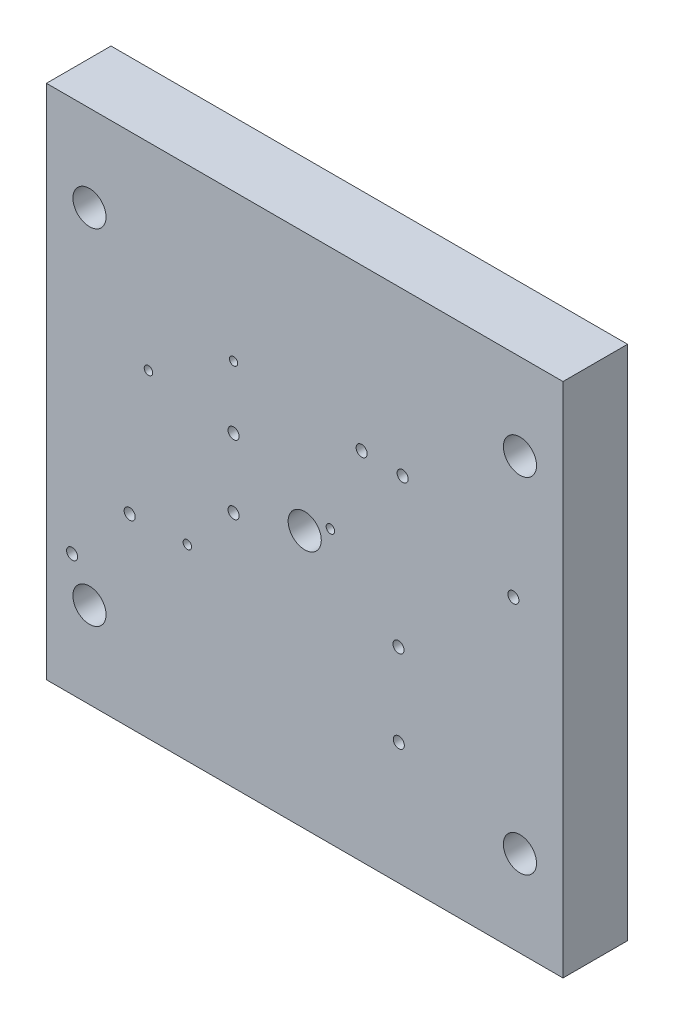
SolidWorks part; units mm, degrees
ref_plane "Front Plane" through (0, 0, 0) normal (0, 0, 1) x (1, 0, 0)
ref_plane "Top Plane" through (0, 0, 0) normal (0, 1, 0) x (1, 0, 0)
ref_plane "Right Plane" through (0, 0, 0) normal (1, 0, 0) x (0, 0, -1)
sketch "Sketch1" plane through (0, 0, 0) normal (0, 0, 1) x (1, 0, 0)
  line L1 (-152.4, 152.4) -> (152.4, 152.4)
  line L2 (-152.4, 152.4) -> (-152.4, -152.4)
  line L3 (-152.4, -152.4) -> (152.4, -152.4)
  line L4 (152.4, 152.4) -> (152.4, -152.4)
  line L5 (-152.4, 152.4) -> (152.4, -152.4) construction
  line L6 (-152.4, -152.4) -> (152.4, 152.4) construction
  point P0 (0, 0)
  dimension "D1" = 304.8
  dimension "D2" = 304.8
extrude "Boss-Extrude1" add sketch "Sketch1" along normal blind 38.1
sketch "Sketch2" plane through (0, 0, 38.1) normal (0, 0, 1) x (1, 0, 0)
  line L0 (-152.4, 0) -> (152.4, 0) construction
  line L5 (-152.4, 152.4) -> (-152.4, -152.4) construction
  line L6 (152.4, -152.4) -> (152.4, 152.4) construction
  line L7 (-152.4, -101.6) -> (152.4, -101.6) construction
  line L8 (-152.4, 101.6) -> (152.4, 101.6) construction
  line L9 (0, 101.6) -> (0, -101.6) construction
  line L10 (127, 101.6) -> (127, -101.6) construction
  line L11 (-127, 101.6) -> (-127, -101.6) construction
  circle A0 centre (-127, 101.6) radius 6.5151
  circle A1 centre (127, 101.6) radius 6.5151
  circle A2 centre (127, -101.6) radius 6.5151
  circle A3 centre (-127, -101.6) radius 6.5151
  circle A4 centre (0, 0) radius 6.5151
  dimension "D5" = 13.0302
  dimension "D1" = 101.6
  dimension "D2" = 101.6
  dimension "D3" = 127
  dimension "D4" = 127
extrude "HAAS T-Slot Holes" cut sketch "Sketch2" against normal through all
sketch "Sketch3" plane through (0, 0, 38.1) normal (0, 0, 1) x (1, 0, 0)
  circle A0 centre (-127, 101.6) radius 9.779
  circle A1 centre (127, 101.6) radius 9.779
  circle A2 centre (0, 0) radius 9.779
  circle A3 centre (127, -101.6) radius 9.779
  circle A4 centre (-127, -101.6) radius 9.779
  dimension "D1" = 19.558
extrude "HAAS Counter Bores" cut sketch "Sketch3" against normal offset from surface (22.225 mm away) 15.875 contours A0 | A1 | A2 | A3 | A4 up to face at (6.5151, 0, 0)
sketch "Sketch4" plane through (0, 0, 38.1) normal (0, 0, 1) x (1, 0, 0)
  circle A1 centre (55.3386, -31.7863) radius 3.2639
  circle A2 centre (55.3386, -31.7863) radius 3.2639
  circle A5 centre (-103.2689, -43.0628) radius 3.2639
  circle A6 centre (-103.2689, -43.0628) radius 3.2639
  circle A7 centre (-41.9849, -11.8461) radius 3.2639
  circle A8 centre (-41.9849, -11.8461) radius 3.2639
  circle A9 centre (-41.9849, 28.7939) radius 3.2639
  circle A10 centre (-41.9849, 28.7939) radius 3.2639
  circle A11 centre (123.1151, 27.5239) radius 3.2639
  circle A12 centre (123.1151, 27.5239) radius 3.2639
  circle A16 centre (-137.2349, -80.4261) radius 3.2639
  circle A17 centre (55.5146, -80.4261) radius 3.2639
  circle A18 centre (33.6023, 57.6321) radius 3.2639
  circle A19 centre (57.7861, 56.7971) radius 3.2639
  dimension "D1" = 0
  dimension "D3" = 0
  dimension "D4" = 0
  dimension "D5" = 0
  dimension "D6" = 0
extrude "Cut-Extrude1" cut sketch "Sketch4" against normal blind 19.05
sketch "Sketch5" plane through (0, 0, 38.1) normal (0, 0, 1) x (1, 0, 0)
  circle A0 centre (-41.9849, 65.6239) radius 2.4146
  circle A1 centre (-92.2093, 35.7436) radius 2.5
  circle A2 centre (-69.2545, -41.7505) radius 2.5
  circle A3 centre (15.1651, 8.4739) radius 2.5
extrude "Cut-Extrude2" cut sketch "Sketch5" against normal blind 12.7
